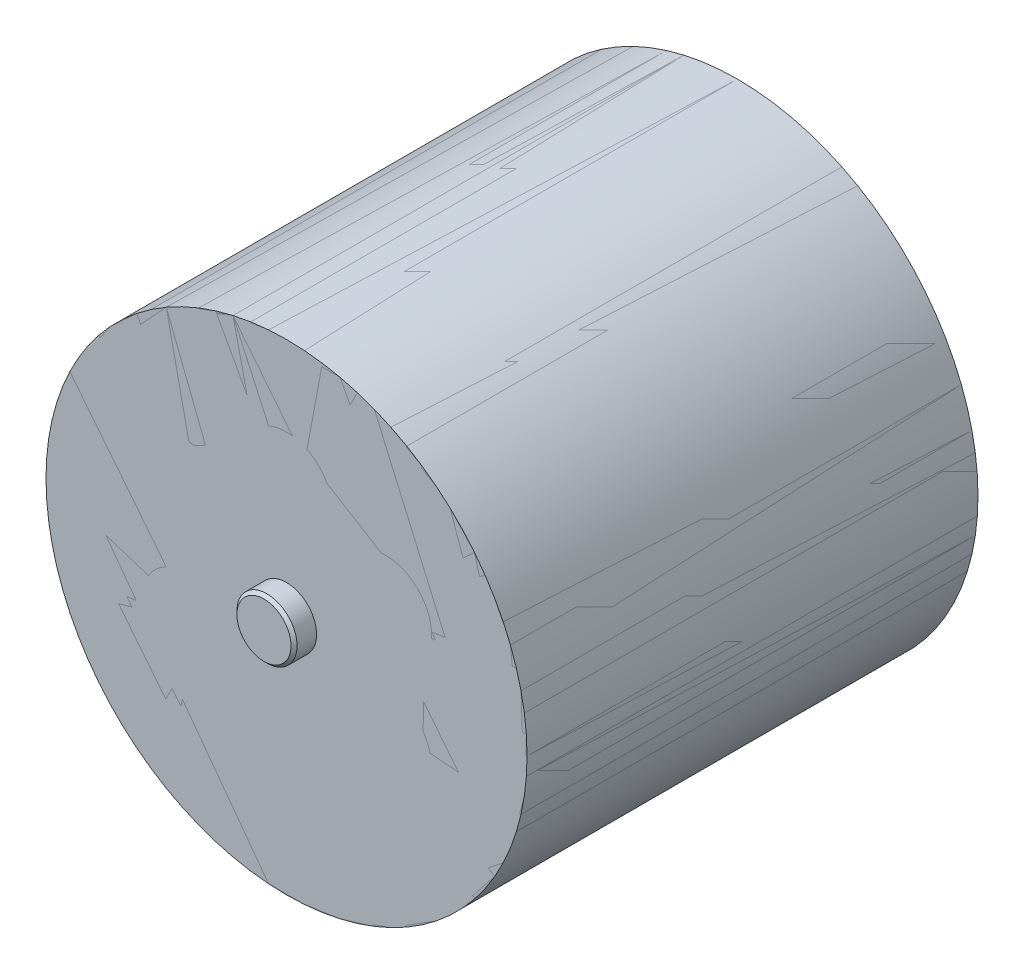
SolidWorks part; units mm, degrees
other "COLL.CYLINDER-Boss-Extrude3"
ref_plane "Piano frontale" through (0, 0, 0) normal (0, 0, 1) x (1, 0, 0)
ref_plane "Piano superiore" through (0, 0, 0) normal (0, 1, 0) x (1, 0, 0)
ref_plane "Piano destro" through (0, 0, 0) normal (1, 0, 0) x (0, 0, -1)
sketch "Sketch1" plane through (0, 0, 0) normal (0, 0, 1) x (1, 0, 0)
  line L0 (271.212, 573.9944) -> (271.212, 413.9944) construction
  circle A0 centre (271.212, 413.9944) radius 160
  dimension "D1" = 320
extrude "Boss-Extrude1" add sketch "Sketch1" against normal mid plane 300
sketch3d "3DSketch1"
  line L0 (271.212, 413.9944, 150) -> (271.212, 413.9944, -150)
  line L1 (271.212, 413.9944, -150) -> (271.212, 413.9944, 150) construction
  line L2 (271.212, 413.9944, 150) -> (271.212, 413.9944, 0)
  line L3 (271.212, 413.9944, 0) -> (271.212, 465.8799, 0)
ref_axis "Axis1" through (271.212, 413.9944, 150) along (0, 0, -1)
sketch "Sketch2" plane through (0, 0, 150) normal (0, 0, 1) x (1, 0, 0)
  line L0 (271.212, 413.9944) -> (271.212, 490.0656) construction
  circle A0 centre (271.212, 490.0656) radius 30.584
extrude "Cut-Extrude1" cut sketch "Sketch2" against normal blind 5
pattern_circular "CirPattern1" count 6 over 360 of "Cut-Extrude1"
mirror "Mirror1" about plane through (0, 0, 0) normal (0, 0, 1) of "CirPattern1"
sketch "Sketch3" plane through (0, 0, 150) normal (0, 0, 1) x (1, 0, 0)
  circle A0 centre (271.212, 413.9944) radius 20
extrude "Boss-Extrude2" add sketch "Sketch3" along normal blind 15
chamfer "Chamfer1" distance 2 angle 45 1 edges at (291.212, 413.9944, 165)
mirror "Mirror4" about plane through (0, 0, 0) normal (0, 0, 1) of "Boss-Extrude2"
sketch "Sketch4" plane through (0, 0, 150) normal (0, 0, 1) x (1, 0, 0)
  circle A0 centre (271.212, 413.9944) radius 160 construction
  circle A1 centre (271.212, 413.9944) radius 160
extrude "Boss-Extrude3" add sketch "Sketch4" against normal up to surface (300 mm away) separate body up to face at (291.212, 413.9944, -150)
